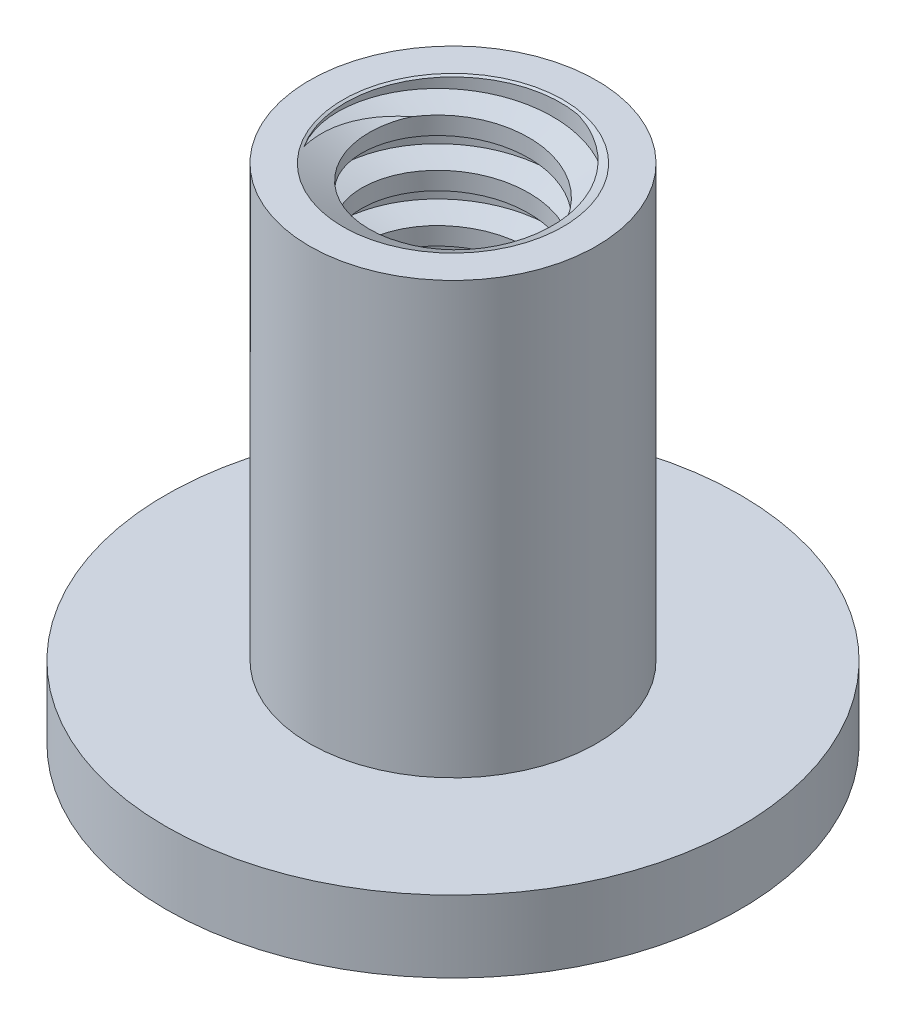
SolidWorks part; units mm, degrees
ref_plane "Front Plane" through (0, 0, 0) normal (0, 0, 1) x (1, 0, 0)
ref_plane "Top Plane" through (0, 0, 0) normal (0, 1, 0) x (1, 0, 0)
ref_plane "Right Plane" through (0, 0, 0) normal (1, 0, 0) x (0, 0, -1)
sketch "Sketch1" plane through (0, 0, 0) normal (0, 1, 0) x (1, 0, 0)
  circle A0 centre (0, 0) radius 12.7
  circle A1 centre (0, 0) radius 6.35 construction
  circle A2 centre (0, 0) radius 4.7625 construction
  dimension "D1" = 12.7
  dimension "OD" = 25.4
  dimension "Thread OD" = 9.525
extrude "Boss-Extrude1" add sketch "Sketch1" along normal blind 22.225
sketch "Sketch2" plane through (0, 22.225, 0) normal (0, 1, 0) x (1, 0, 0)
  circle A0 centre (0, 0) radius 4.7625 construction
  circle A1 centre (0, 0) radius 4.7625
extrude "Cut-Extrude1" cut sketch "Sketch2" against normal up to next
sketch "Sketch3" plane through (0, 22.225, 0) normal (0, 1, 0) x (1, 0, 0)
  circle A1 centre (0, 0) radius 4.7625
  circle A2 centre (0, 0) radius 4.7625
  point P0 (0, 4.7625)
  dimension "D1" = 0
curve "Helix/Spiral1" pitch 2.1167 height 24.3417 turns 11.5 parameters "Pitch"=2.1167
sketch "Sketch4" plane through (0, 0, 0) normal (1, 0, 0) x (0, 0, -1)
  line L0 (4.7625, 23.557) -> (3.7042, 23.2833)
  line L1 (3.7042, 23.2833) -> (3.7042, 22.4987)
  line L2 (3.7042, 22.4987) -> (4.7625, 22.225)
  line L3 (4.7625, 22.225) -> (4.7625, 23.557)
  line L4 (4.2333, 23.4202) -> (4.2333, 22.3619) construction
  line L7 (3.7042, 22.891) -> (4.7625, 22.891) construction
  line L8 (4.7625, 22.225) -> (4.7625, 21.4404) construction
  dimension "a" = 14.5
  dimension "2A" = 29
  dimension "p" = 2.1167
  dimension "t" = 1.0583
  dimension "h" = 1.0583
sweep "Sweep1" add profiles "Sketch4" path "Helix/Spiral1"
sketch "Sketch5" plane through (0, 22.225, 0) normal (0, 1, 0) x (1, 0, 0)
  line L0 (-3.4424, 3.4424) -> (0, 0) construction
  line L1 (0, 0) -> (0, 4.8683) construction
  circle A0 centre (0, 0) radius 4.7625 construction
  circle A1 centre (0, 0) radius 4.8683
  dimension "D2" = 45
  dimension "D1" = 0.1058
extrude "Cut-Extrude3" cut sketch "Sketch5" against normal through all draft 60 and the other way through all draft 60
sketch "Sketch6" plane through (0, 0, 0) normal (0, -1, 0) x (1, 0, 0)
  circle A1 centre (0, 0) radius 4.8683
  circle A2 centre (0, 0) radius 4.8683
  dimension "D1" = 0
extrude "Cut-Extrude4" cut sketch "Sketch6" against normal through all draft 60 and the other way through all draft 60
sketch "Sketch7" plane through (0, 22.225, 0) normal (0, 1, 0) x (1, 0, 0)
  circle A0 centre (0, 0) radius 6.35 construction
  circle A2 centre (0, 0) radius 6.35
extrude "Cut-Extrude5" cut sketch "Sketch7" against normal offset from surface (19.05 mm away) 3.175 flip side to cut up to face at (0, 0, 4.8683)
equation "\"D3@Helix/Spiral1\" = \"Pitch@Helix/Spiral1\" + \"Ht.@Boss-Extrude1\""
equation "\"p@Sketch4\" = \"Pitch@Helix/Spiral1\""
equation "\"h@Sketch4\" = \"p@Sketch4\" / 2"
equation "\"t@Sketch4\" = \"p@Sketch4\" / 2"
equation "\"D1@Sketch5\" = \"Pitch@Helix/Spiral1\" * 0.05"
